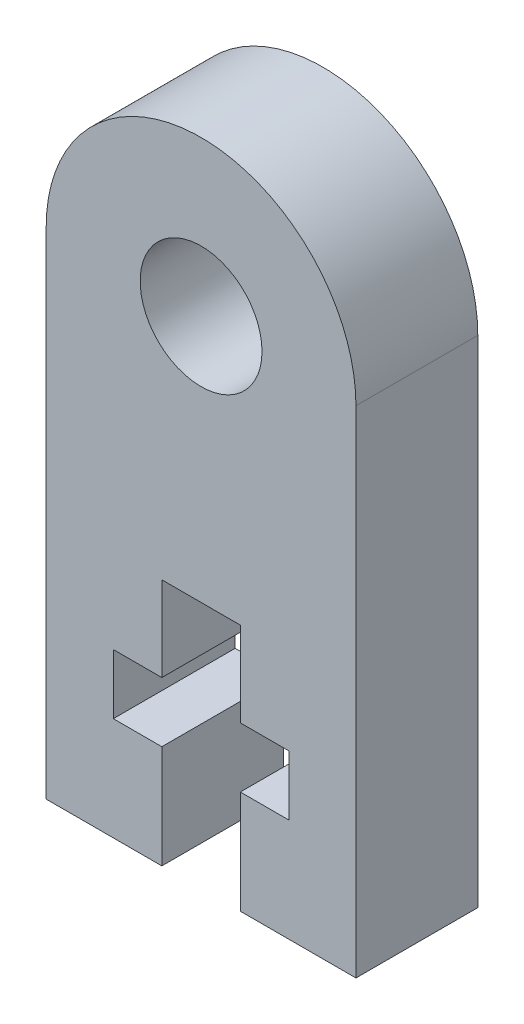
SolidWorks part; units mm, degrees
ref_plane "Front Plane" through (0, 0, 0) normal (0, 0, 1) x (1, 0, 0)
ref_plane "Top Plane" through (0, 0, 0) normal (0, 1, 0) x (1, 0, 0)
ref_plane "Right Plane" through (0, 0, 0) normal (1, 0, 0) x (0, 0, -1)
sketch "Sketch1" plane through (0, 0, 0) normal (0, 0, 1) x (1, 0, 0)
  line L0 (0, 0) -> (-2.086, 2.086) construction
  line L1 (0, 0) -> (0, 2.95) construction
  line L2 (-7.5, 0) -> (-7.5, -24)
  line L3 (-7.5, -24) -> (7.5, -24)
  line L4 (7.5, -24) -> (7.5, 0)
  line L5 (0, 0) -> (0, -24) construction
  circle A0 centre (0, 0) radius 2.95
  arc A1 (-7.5, 0) -> (7.5, 0) centre (0, 0) cw
  dimension "D1" = 5.9
  dimension "D4" = 45
  dimension "D5" = 24
  dimension "D6" = 15
extrude "Boss-Extrude1" add sketch "Sketch1" along normal blind 5.9
sketch "Sketch3" plane through (0, 0, 5.9) normal (0, 0, 1) x (1, 0, 0)
  line L0 (-7.5, -24) -> (7.5, -24) construction
  line L1 (-1.9, -24) -> (1.9, -24)
  line L2 (-1.9, -24) -> (-1.9, -19)
  line L3 (-1.9, -12) -> (1.9, -12)
  line L4 (1.9, -24) -> (1.9, -19)
  line L5 (0, -12) -> (0, 0) construction
  line L6 (1.9, -16.1) -> (4.25, -16.1)
  line L7 (-4.25, -16.1) -> (-1.9, -16.1)
  line L8 (-4.25, -16.1) -> (-4.25, -19)
  line L9 (-4.25, -19) -> (-1.9, -19)
  line L10 (4.25, -16.1) -> (4.25, -19)
  line L11 (-1.9, -16.1) -> (-1.9, -12)
  line L12 (1.9, -19) -> (4.25, -19)
  line L13 (1.9, -16.1) -> (1.9, -12)
  point P18 (-3.075, -19)
  dimension "D1" = 3.8
  dimension "D3" = 12
  dimension "D4" = 8.5
  dimension "D5" = 2.9
  dimension "D6" = 5
extrude "Cut-Extrude2" cut sketch "Sketch3" against normal through all
equation "\"smallPulleyTeeth\"= 15"
equation "\"largePulleyTeeth\"= 40"
equation "\"eighthThick\"= 2.9mm"
equation "\"sixteenthThick\"= 1.7mm"
equation "\"quarterThick\"=5.9mm"
equation "\"OD\"= 145mm"
equation "\"puckAngle\"= 60.5deg"
equation "\"puckDiam\"= 76.5mm"
equation "\"axlePress\"= 5.9mm"
equation "\"D1@Sketch1\"=\"axlePress\""
equation "\"D1@Boss-Extrude1\"=\"quarterThick\""
equation "\"press\"= 0.2mm"
equation "\"wheelClear\"= 0.3mm"
equation "\"10-32clear\"= 4.5mm"
equation "\"D1@Sketch3\"=\"8-32clear\"-\"press\""
equation "\"6-32clear\"= 3.3mm"
equation "\"8-32clear\"= 4.0mm"
equation "\"wheelHeight\"= 24mm"
equation "\"D5@Sketch1\"=\"wheelHeight\""
equation "\"wheelWell\"= 62mm"
